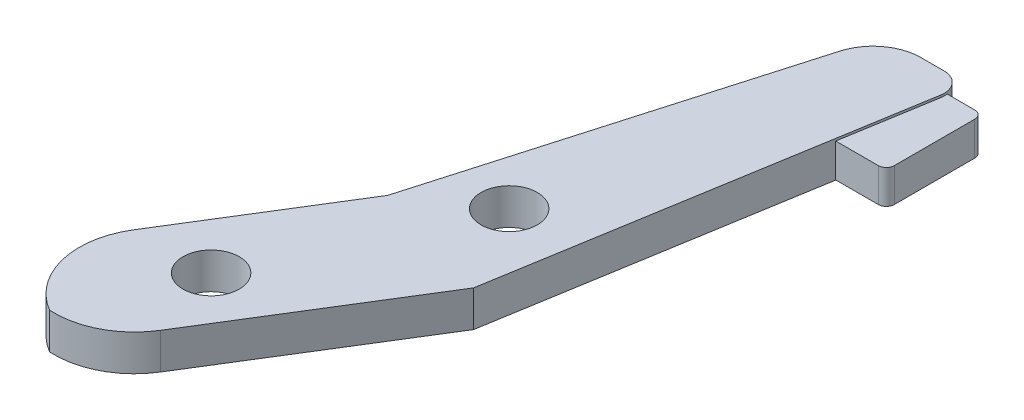
SolidWorks part; units mm, degrees
ref_plane "Front Plane" through (0, 0, 0) normal (0, 0, 1) x (1, 0, 0)
ref_plane "Top Plane" through (0, 0, 0) normal (0, 1, 0) x (1, 0, 0)
ref_plane "Right Plane" through (0, 0, 0) normal (1, 0, 0) x (0, 0, -1)
sketch "Sketch1" plane through (0, 0, 0) normal (0, 1, 0) x (1, 0, 0)
  line L0 (0, 0) -> (9.4812, 15.3005)
  line L1 (9.4812, 15.3005) -> (16.4036, 39.323)
  line L6 (17.1409, 12.992) -> (7.6597, -2.3085)
  line L7 (7.6597, -2.3085) -> (0, 0)
  line L9 (17.1409, 12.992) -> (21.5168, 39.323)
  line L10 (21.5168, 39.323) -> (16.4036, 39.323)
  dimension "D1" = 8
  dimension "D2" = 18
  dimension "D3" = 18
  dimension "D4" = 25
extrude "Boss-Extrude1" add sketch "Sketch1" along normal blind 2.25
fillet "Fillet1" radius 5 2 edges at (7.6597, 1.125, 2.3085) (0, 1.125, 0)
sketch "Sketch2" plane through (0, 2.25, 0) normal (0, 1, 0) x (1, 0, 0)
  line L0 (17.1409, 12.992) -> (21.5168, 39.323) construction
  line L1 (9.6801, 0.952) -> (17.1409, 12.992) construction
  circle A0 centre (8.1672, 5.6299) radius 1.75
  circle A1 centre (13.9792, 18.3665) radius 1.75
  dimension "D1" = 3.5
  dimension "D2" = 3.5
  dimension "D3" = 14
  dimension "D4" = 4
  dimension "D5" = 3.75
extrude "Cut-Extrude1" cut sketch "Sketch2" against normal through all
ref_plane "Plane1" through (23.5, 0, 0) normal (1, 0, 0) x (0, 0, -1)
sketch "Sketch4" plane through (23.5, -1.4847, -8.2019) normal (1, 0, 0) x (0, 0, -1)
  line L1 (30.1151, 3.5919) -> (24.1151, 3.5919)
  line L2 (30.1151, 3.5919) -> (30.1151, 1.4919)
  line L3 (30.1151, 1.4919) -> (24.1151, 1.4919)
  line L4 (24.1151, 3.5919) -> (24.1151, 1.4919)
  dimension "D1" = 2.1
  dimension "D2" = 6
extrude "Boss-Extrude2" add sketch "Sketch4" against normal up to surface (2.1504 mm away) up to face at (19.3289, 1.125, -26.1575)
extrude "Boss-Extrude3" add sketch "Sketch4<2>" against normal up to surface (2.1504 mm away) up to face at (20.851, 1.0572, -35.3169)
sketch "Sketch4<2>" plane through (23.5, -1.4847, -8.2019) normal (1, 0, 0) x (0, 0, -1) same geometry as "Sketch4"
fillet "Fillet2" radius 3 1 edges at (16.4036, 1.125, -39.323)
fillet "Fillet3" radius 1.2 1 edges at (21.5168, 1.125, -39.323)
fillet "Fillet4" radius 0.5 2 edges at (23.5, 1.0572, -32.3169) (23.5, 1.0572, -38.3169)
